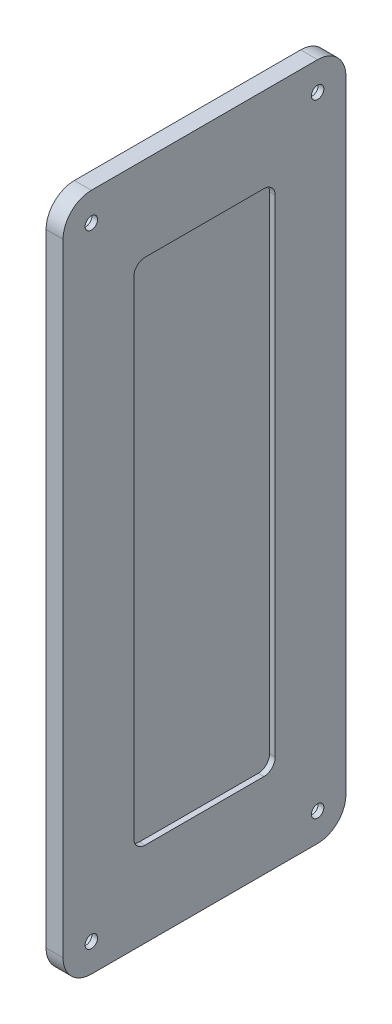
SolidWorks part; units mm, degrees
ref_plane "Front Plane" through (0, 0, 0) normal (0, 0, 1) x (1, 0, 0)
ref_plane "Top Plane" through (0, 0, 0) normal (0, 1, 0) x (1, 0, 0)
ref_plane "Right Plane" through (0, 0, 0) normal (1, 0, 0) x (0, 0, -1)
sketch "Sketch1" plane through (0, 0, 0) normal (1, 0, 0) x (0, 0, -1)
  line L1 (-25, 60) -> (25, 60)
  line L2 (-25, 60) -> (-25, -60)
  line L3 (-25, -60) -> (25, -60)
  line L4 (25, 60) -> (25, -60)
  line L5 (-12.5, 45) -> (12.5, 45)
  line L6 (-12.5, 45) -> (-12.5, -45)
  line L7 (-12.5, -45) -> (12.5, -45)
  line L8 (12.5, 45) -> (12.5, -45)
  dimension "D1" = 120
  dimension "D2" = 50
  dimension "D3" = 25
  dimension "D4" = 60
  dimension "D5" = 25
  dimension "D6" = 90
  dimension "D7" = 45
  dimension "D8" = 12.5
extrude "Boss-Extrude1" add sketch "Sketch1" along normal blind 3
extrude "Boss-Extrude2" add sketch "Sketch1<3>" along normal blind 2 contours L8 L7 L6 L5
sketch "Sketch1<3>" plane through (0, 0, 0) normal (1, 0, 0) x (0, 0, -1) same geometry as "Sketch1"
sketch "Sketch2" plane through (0, 0, 0) normal (-1, 0, 0) x (0, 0, 1)
  line L0 (-25, -60) -> (-25, 60) construction
  line L1 (-25, 60) -> (25, 60) construction
  line L2 (25, 60) -> (25, -60) construction
  line L3 (25, -60) -> (-25, -60) construction
  circle A0 centre (-20, 55) radius 2
  circle A1 centre (20, 55) radius 2
  circle A2 centre (-20, -55) radius 2
  circle A3 centre (20, -55) radius 2
  point P12 (0, 0)
  point P15 (0, 0)
  point P18 (0, 0)
  point P19 (0, 0)
  dimension "D3" = 4
  dimension "D4" = 5
  dimension "D5" = 5
  dimension "D1" = 5
  dimension "D2" = 5
extrude "Cut-Extrude1" cut sketch "Sketch2" against normal blind 2
sketch "Sketch3" plane through (0, 0, 0) normal (-1, 0, 0) x (0, 0, 1)
  circle A0 centre (-20, 55) radius 1.1
  circle A1 centre (20, 55) radius 1.1
  circle A2 centre (-20, -55) radius 1.1
  circle A3 centre (20, -55) radius 1.1
  dimension "D1" = 2.2
extrude "Cut-Extrude2" cut sketch "Sketch3" against normal blind 3
fillet "Fillet1" radius 5 4 edges at (1.5, -60, 25) (1.5, -60, -25) (1.5, 60, -25) (1.5, 60, 25)
fillet "Fillet2" radius 2 4 edges at (2.5, 45, 12.5) (2.5, -45, 12.5) (2.5, -45, -12.5) (2.5, 45, -12.5)
